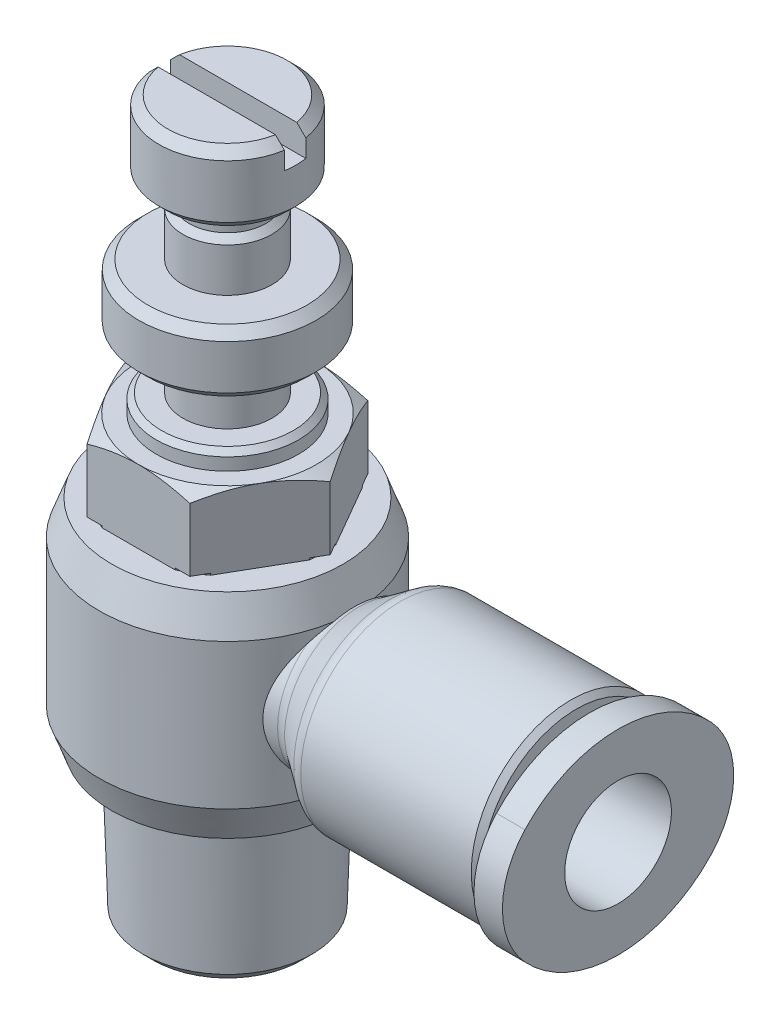
SolidWorks part; units mm, degrees
ref_plane "Front" through (0, 0, 0) normal (0, 0, 1) x (1, 0, 0)
ref_plane "Top" through (0, 0, 0) normal (0, 1, 0) x (1, 0, 0)
ref_plane "Right" through (0, 0, 0) normal (1, 0, 0) x (0, 0, -1)
ref_plane "Plane1" through (0, 0, 0) normal (0, 0, 1) x (1, 0, 0)
sketch "Sketch1" plane through (0, 0, 0) normal (0, 0, 1) x (1, 0, 0)
  line L0 (19.6, 0) -> (19.6, -5.3)
  line L1 (19.6, -5.3) -> (19.3, -5.6)
  line L2 (19.3, -5.6) -> (9.7176, -5.6)
  line L3 (9.1406, -5.4168) -> (7.3944, -4.1832)
  line L4 (6.8174, -4) -> (0, -4)
  line L5 (0, -4) -> (0, 0)
  line L6 (0, 0) -> (19.6, 0)
  line L7 (0, 0) -> (19.6, 0) construction
  arc A0 (9.7176, -5.6) -> (9.1406, -5.4168) centre (9.7176, -4.6) cw
  arc A1 (7.3944, -4.1832) -> (6.8174, -4) centre (6.8174, -5) ccw
revolve "Revolve1" add sketch "Sketch1" angle 360 about L7 reverse direction yes
ref_plane "Plane2" through (0, 0, 0) normal (0, 0, 1) x (1, 0, 0)
sketch "Sketch2" plane through (0, 0, 0) normal (0, 0, 1) x (1, 0, 0)
  line L0 (0, -6.2) -> (-6.5, -6.2)
  line L1 (-6.5, -6.2) -> (-7.2, -4.277)
  line L2 (-7.2, -4.277) -> (-7.2, 3.877)
  line L3 (-7.2, 3.877) -> (-6.5, 5.8)
  line L4 (-6.5, 5.8) -> (0, 5.8)
  line L5 (0, 5.8) -> (0, -6.2)
  line L6 (0, 5.8) -> (0, -6.2) construction
revolve "Revolve2" add sketch "Sketch2" angle 360 about L6 reverse direction yes
ref_plane "Plane3" through (0, 0, 0) normal (0, 0, 1) x (1, 0, 0)
sketch "Sketch3" plane through (0, 0, 0) normal (0, 0, 1) x (1, 0, 0)
  line L0 (0, 5.8) -> (-5.4, 5.8)
  line L1 (-5.4, 5.8) -> (-5.4, 5.9)
  line L2 (-5.4, 5.9) -> (-5.774, 5.9)
  line L3 (-5.774, 5.9) -> (-5.774, 9.9)
  line L4 (-5.774, 9.9) -> (-4, 9.9)
  line L5 (-4, 9.9) -> (-4, 10.6)
  line L6 (-4, 10.6) -> (-3.7, 10.9)
  line L7 (-3.7, 10.9) -> (-2.5, 10.9)
  line L8 (-2.5, 10.9) -> (-2.5, 13.9)
  line L9 (-2.5, 13.9) -> (-4.477, 13.9)
  line L10 (-4.477, 13.9) -> (-4.977, 14.4)
  line L11 (-4.977, 14.4) -> (-4.977, 16.9)
  line L12 (-4.977, 16.9) -> (-4.477, 17.4)
  line L13 (-4.477, 17.4) -> (-2.5, 17.4)
  line L14 (-2.5, 17.4) -> (-2.5, 19.85)
  line L15 (-2.5, 19.85) -> (-2.15, 20.2)
  line L16 (-2.15, 20.2) -> (-2.15, 21.4)
  line L17 (-2.15, 21.4) -> (-3.35, 21.4)
  line L18 (-3.35, 21.4) -> (-3.85, 21.9)
  line L19 (-3.85, 21.9) -> (-3.85, 24.9)
  line L20 (-3.85, 24.9) -> (-3.35, 25.4)
  line L21 (-3.35, 25.4) -> (0, 25.4)
  line L22 (0, 25.4) -> (0, 5.8)
  line L23 (0, 25.4) -> (0, 5.8) construction
revolve "Revolve3" add sketch "Sketch3" angle 360 about L23 reverse direction yes
ref_plane "Plane4" through (0, 9.9, 0) normal (0, 1, 0) x (-1, 0, 0)
sketch "Sketch4" plane through (0, 9.9, 0) normal (0, 1, 0) x (-1, 0, 0)
  line L0 (5.7735, 0) -> (2.8868, 5)
  line L1 (2.8868, 5) -> (-2.8868, 5)
  line L2 (-2.8868, 5) -> (-5.7735, 0)
  line L3 (-5.7735, 0) -> (-2.8868, -5)
  line L4 (-2.8868, -5) -> (2.8868, -5)
  line L5 (2.8868, -5) -> (5.7735, 0)
  circle A0 centre (0, 0) radius 7
extrude "Cut-Extrude1" cut sketch "Sketch4" against normal blind 4.1
ref_plane "Plane5" through (0, 0, 0) normal (0, 0, 1) x (1, 0, 0)
sketch "Sketch5" plane through (0, 0, 0) normal (0, 0, 1) x (1, 0, 0)
  line L0 (-7, 8.7453) -> (-5, 9.9)
  line L1 (-5, 9.9) -> (-7, 9.9)
  line L2 (-7, 9.9) -> (-7, 8.7453)
  line L3 (0, 50) -> (0, -50) construction
revolve "Cut-Revolve1" cut sketch "Sketch5" angle 360 about L3 reverse direction yes
ref_plane "Plane6" through (0, 0, 0) normal (1, 0, 0) x (0, 0, -1)
sketch "Sketch6" plane through (0, 0, 0) normal (1, 0, 0) x (0, 0, -1)
  line L0 (-0.6, 25.4) -> (-0.6, 23.9)
  line L1 (-0.6, 23.9) -> (0.6, 23.9)
  line L2 (0.6, 23.9) -> (0.6, 25.4)
  line L3 (0.6, 25.4) -> (-0.6, 25.4)
extrude "Cut-Extrude2" cut sketch "Sketch6" against normal blind 4.3 and the other way blind 4.3
ref_plane "Plane7" through (0, 0, 0) normal (0, 0, 1) x (1, 0, 0)
sketch "Sketch7" plane through (0, 0, 0) normal (0, 0, 1) x (1, 0, 0)
  line L0 (0, -6.2) -> (5, -6.2)
  line L1 (5, -6.2) -> (5, -6.3)
  line L2 (5, -6.3) -> (5.15, -6.3)
  line L3 (5.15, -6.3) -> (5.15, -6.35)
  line L4 (5.15, -6.35) -> (5, -7)
  line L5 (5, -7) -> (0, -7)
  line L6 (0, -7) -> (0, -6.2)
  line L7 (0, -7) -> (0, -6.2) construction
revolve "Revolve4" add sketch "Sketch7" angle 360 about L7 reverse direction yes
ref_plane "Plane8" through (0, 0, 0) normal (0, 0, 1) x (1, 0, 0)
sketch "Sketch8" plane through (0, 0, 0) normal (0, 0, 1) x (1, 0, 0)
  line L0 (0, -6.3) -> (4.9998, -6.3)
  line L1 (4.9998, -6.3) -> (4.7578, -14.0503)
  line L2 (4.7578, -14.0503) -> (4.1581, -14.65)
  line L3 (4.1581, -14.65) -> (0, -14.65)
  line L4 (0, -14.65) -> (0, -6.3)
  line L5 (0, -14.65) -> (0, -6.3) construction
revolve "Revolve5" add sketch "Sketch8" angle 360 about L5 reverse direction yes
ref_plane "Plane9" through (0, 0, 0) normal (0, 0, 1) x (1, 0, 0)
sketch "Sketch9" plane through (0, 0, 0) normal (0, 0, 1) x (1, 0, 0)
  line L0 (-3.2427, 0) -> (-3.2427, 3)
  line L1 (-3.2427, 3) -> (21.95, 3)
  line L2 (21.95, 3) -> (21.95, 0)
  line L3 (21.95, 0) -> (-3.2427, 0)
  line L4 (21.95, 0) -> (-3.2427, 0) construction
revolve "Cut-Revolve2" cut sketch "Sketch9" angle 360 about L4 reverse direction yes
ref_plane "Plane10" through (0, 0, 0) normal (0, 0, 1) x (1, 0, 0)
sketch "Sketch10" plane through (0, 0, 0) normal (0, 0, 1) x (1, 0, 0)
  line L0 (0, -14.65) -> (-3.2427, -14.65)
  line L1 (-3.2427, -14.65) -> (-3.2427, 0)
  line L2 (-3.2427, 0) -> (0, 0)
  line L3 (0, 0) -> (0, -14.65)
  line L4 (0, 0) -> (0, -14.65) construction
revolve "Cut-Revolve3" cut sketch "Sketch10" angle 360 about L4 reverse direction yes
ref_plane "Plane11" through (0, 0, 0) normal (0, 0, 1) x (1, 0, 0)
sketch "Sketch11" plane through (0, 0, 0) normal (0, 0, 1) x (1, 0, 0)
  line L0 (19.6, 0) -> (19.6, 3.75)
  line L1 (19.6, 3.75) -> (20.35, 3.75)
  line L2 (20.35, 3.75) -> (20.35, 0)
  line L3 (20.35, 0) -> (19.6, 0)
  line L4 (20.35, 0) -> (19.6, 0) construction
revolve "Revolve6" add sketch "Sketch11" angle 360 about L4 reverse direction yes
ref_plane "Plane12" through (21.95, 0, 0) normal (1, 0, 0) x (0, 0, -1)
sketch "Sketch12" plane through (21.95, 0, 0) normal (1, 0, 0) x (0, 0, -1)
  arc A0 (-5.2326, 3.2214) -> (-5.2326, -3.2214) centre (-1.7705, 0) ccw
  arc A1 (-5.2326, -3.2214) -> (5.2326, -3.2214) centre (0, 1.6474) ccw
  arc A2 (5.2326, -3.2214) -> (5.2326, 3.2214) centre (1.7705, 0) ccw
  arc A3 (5.2326, 3.2214) -> (-5.2326, 3.2214) centre (0, -1.6474) ccw
extrude "Boss-Extrude2" add sketch "Sketch12" against normal blind 1.6
ref_plane "Plane13" through (0, 0, 0) normal (0, 0, 1) x (1, 0, 0)
sketch "Sketch13" plane through (0, 0, 0) normal (0, 0, 1) x (1, 0, 0)
  line L0 (21.95, 0) -> (21.95, -3)
  line L1 (21.95, -3) -> (19.6, -3)
  line L2 (19.6, -3) -> (19.6, 0)
  line L3 (19.6, 0) -> (21.95, 0)
  line L4 (19.6, 0) -> (21.95, 0) construction
revolve "Cut-Revolve4" cut sketch "Sketch13" angle 360 about L4 reverse direction yes
